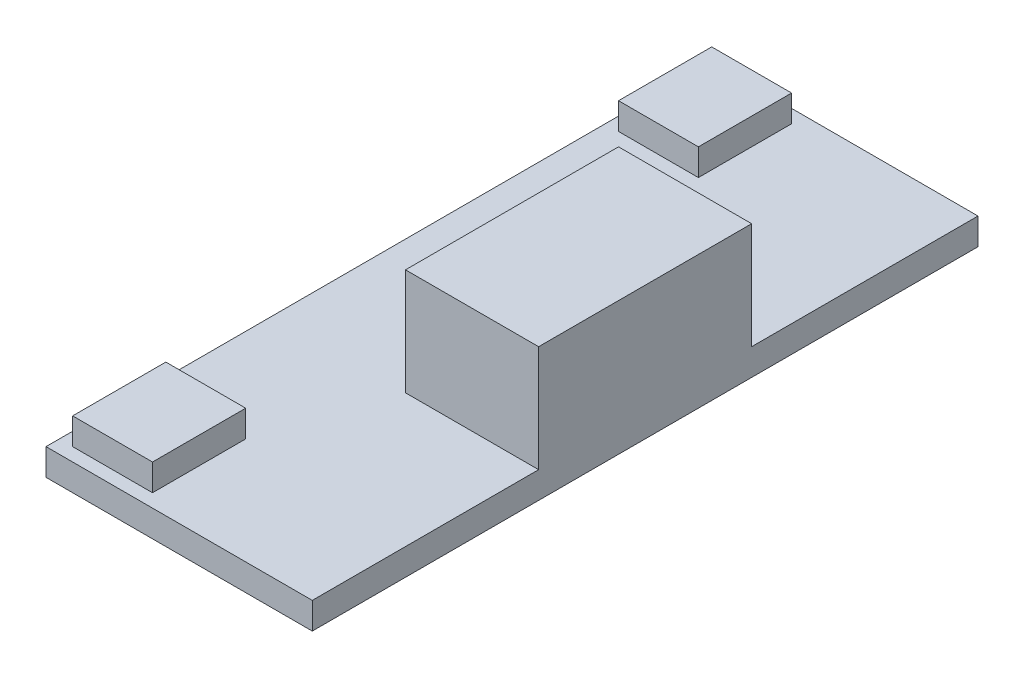
SolidWorks part; units mm, degrees
ref_plane "Front Plane" through (0, 0, 0) normal (0, 0, 1) x (1, 0, 0)
ref_plane "Top Plane" through (0, 0, 0) normal (0, 1, 0) x (1, 0, 0)
ref_plane "Right Plane" through (0, 0, 0) normal (1, 0, 0) x (0, 0, -1)
sketch "Sketch1" plane through (0, 0, 0) normal (0, 1, 0) x (1, 0, 0)
  line L1 (5, -12.5) -> (-5, -12.5)
  line L2 (5, -12.5) -> (5, 12.5)
  line L3 (5, 12.5) -> (-5, 12.5)
  line L4 (-5, -12.5) -> (-5, 12.5)
  line L5 (5, -12.5) -> (-5, 12.5) construction
  line L6 (5, 12.5) -> (-5, -12.5) construction
  point P0 (0, 0)
  dimension "D1" = 25
  dimension "D2" = 10
extrude "Boss-Extrude1" add sketch "Sketch1" along normal blind 1
sketch "Sketch2" plane through (0, 1, 0) normal (0, 1, 0) x (1, 0, 0)
  line L0 (-5, 12.5) -> (-5, -12.5) construction
  line L1 (-4.5, -12) -> (-1.5, -12)
  line L2 (-4.5, -12) -> (-4.5, -8.5)
  line L3 (-4.5, -8.5) -> (-1.5, -8.5)
  line L4 (-1.5, -12) -> (-1.5, -8.5)
  line L5 (-5, -12.5) -> (5, -12.5) construction
  line L6 (-0.55, 0) -> (0.55, 0) construction
  line L7 (-4.5, 8.5) -> (-1.5, 8.5)
  line L8 (-1.5, 12) -> (-1.5, 8.5)
  line L9 (-4.5, 12) -> (-1.5, 12)
  line L10 (-4.5, 12) -> (-4.5, 8.5)
  line L11 (5, -12.5) -> (5, 12.5) construction
  line L12 (0, 4) -> (5, 4)
  line L13 (0, 4) -> (0, -4)
  line L14 (0, -4) -> (5, -4)
  line L15 (5, 4) -> (5, -4)
  point P21 (0, 0)
  dimension "D1" = 3
  dimension "D2" = 3.5
  dimension "D3" = 0.5
  dimension "D4" = 0.5
  dimension "D5" = 8
  dimension "D6" = 5
extrude "Boss-Extrude2" add sketch "Sketch2" along normal blind 4 contours L13 L12 L15 L14
extrude "Boss-Extrude3" add sketch "Sketch2<3>" along normal blind 1 contours L1 L4 L3 L2 | L9 L10 L7 L8 region at (-3, 1, 10.25) region at (-3, 1, -10.25)
sketch "Sketch2<3>" plane through (0, 1, 0) normal (0, 1, 0) x (1, 0, 0) same geometry as "Sketch2"
